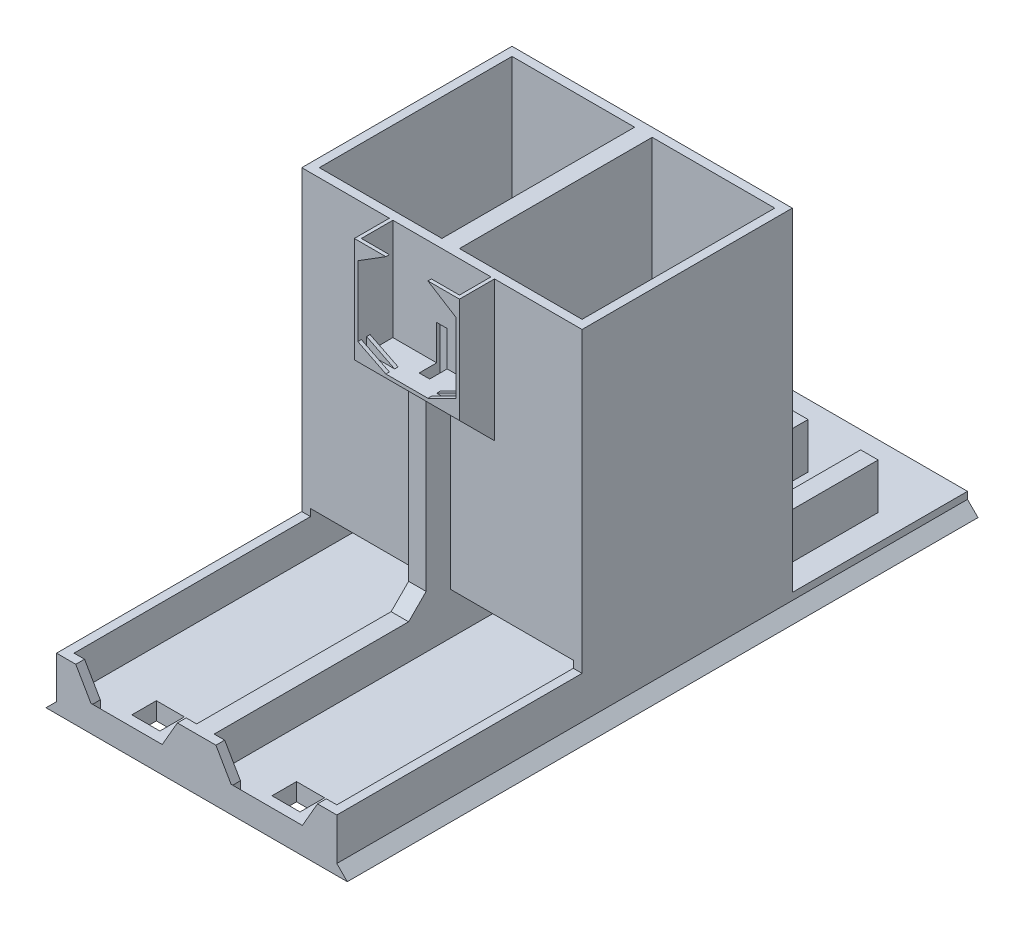
SolidWorks part; units mm, degrees
ref_plane "Front Plane" through (0, 0, 0) normal (0, 0, 1) x (1, 0, 0)
ref_plane "Top Plane" through (0, 0, 0) normal (0, 1, 0) x (1, 0, 0)
ref_plane "Right Plane" through (0, 0, 0) normal (1, 0, 0) x (0, 0, -1)
sketch "Sketch1" plane through (0, 0, 0) normal (0, 1, 0) x (1, 0, 0)
  line L1 (0, 0) -> (80, 0)
  line L2 (0, 0) -> (0, 60)
  line L3 (0, 60) -> (80, 60)
  line L4 (80, 0) -> (80, 60)
sketch "Sketch2" plane through (0, 0, 0) normal (0, 1, 0) x (1, 0, 0)
  line L1 (2.5, 57.5) -> (37.5, 57.5)
  line L2 (2.5, 57.5) -> (2.5, 2.5)
  line L3 (2.5, 2.5) -> (37.5, 2.5)
  line L4 (37.5, 57.5) -> (37.5, 2.5)
  line L5 (42.5, 57.5) -> (77.5, 57.5)
  line L6 (42.5, 57.5) -> (42.5, 2.5)
  line L7 (42.5, 2.5) -> (77.5, 2.5)
  line L8 (77.5, 57.5) -> (77.5, 2.5)
  dimension "D1" = 35
extrude "Boss-Extrude1" add sketch "Sketch1" along normal blind 100
extrude "Cut-Extrude1" cut sketch "Sketch2" along normal blind 95 from offset 5
sketch "Sketch3" plane through (0, 0, 0) normal (0, 0, 1) x (1, 0, 0)
  line L0 (80, 100) -> (80, 0) construction
  line L1 (0, 0) -> (80, 0)
  line L2 (0, 0) -> (0, 5)
  line L3 (0, 5) -> (80, 5)
  line L4 (80, 0) -> (80, 5)
extrude "Boss-Extrude2" add sketch "Sketch3" along normal blind 70
sketch "Sketch4" plane through (0, 5, 0) normal (0, 1, 0) x (1, 0, 0)
  line L0 (80, 0) -> (77.5, 0)
  line L5 (0, 0) -> (0, -70)
  line L18 (0, -70) -> (80, -70)
  line L19 (80, -70) -> (80, 0)
  line L20 (80, 0) -> (0, 0) construction
  line L21 (77.5, 0) -> (77.5, -67.5)
  line L22 (77.5, -67.5) -> (42.5, -67.5)
  line L23 (42.5, -67.5) -> (42.5, 0)
  line L24 (0, 0) -> (80, 0) construction
  line L25 (42.5, 0) -> (37.5, 0)
  line L26 (37.5, 0) -> (37.5, -67.5)
  line L27 (37.5, -67.5) -> (2.5, -67.5)
  line L28 (2.5, -67.5) -> (2.5, 0)
  line L29 (2.5, 0) -> (0, 0)
extrude "Boss-Extrude3" add sketch "Sketch4" along normal blind 10
sketch "Sketch5" plane through (0, 15, 0) normal (0, 1, 0) x (1, 0, 0)
  line L0 (37.5, -67.5) -> (2.5, -67.5) construction
  line L1 (10, -67.5) -> (30, -67.5)
  line L2 (10, -67.5) -> (10, -70)
  line L3 (10, -70) -> (30, -70)
  line L4 (30, -67.5) -> (30, -70)
  line L5 (0, -70) -> (80, -70) construction
  line L6 (77.5, -67.5) -> (42.5, -67.5) construction
  line L7 (70, -67.5) -> (50, -67.5)
  line L8 (70, -67.5) -> (70, -70)
  line L9 (70, -70) -> (50, -70)
  line L10 (50, -67.5) -> (50, -70)
  line L12 (37.5, 0) -> (37.5, -67.5) construction
  line L13 (42.5, -67.5) -> (42.5, 0) construction
  line L14 (77.5, 0) -> (77.5, -67.5) construction
  line L15 (2.5, -67.5) -> (2.5, 0) construction
  dimension "D1" = 7.5
  dimension "D2" = 7.5
  dimension "D3" = 7.5
  dimension "D4" = 7.5
extrude "Cut-Extrude2" cut sketch "Sketch5" against normal blind 7.5
sketch "Sketch6" plane through (0, 0, 0) normal (0, 0, 1) x (1, 0, 0)
  line L1 (2.5, 17) -> (37.5, 17)
  line L2 (2.5, 17) -> (2.5, 5)
  line L3 (2.5, 5) -> (37.5, 5)
  line L4 (37.5, 17) -> (37.5, 5)
  line L5 (42.5, 5) -> (77.5, 5)
  line L6 (42.5, 5) -> (42.5, 17)
  line L7 (42.5, 17) -> (77.5, 17)
  line L8 (77.5, 5) -> (77.5, 17)
extrude "Cut-Extrude4" cut sketch "Sketch6" against normal blind 57.5
sketch "Sketch7" plane through (0, 0, -60) normal (0, 0, -1) x (-1, 0, 0)
  circle A0 centre (-20, 11.5) radius 4
  circle A1 centre (-60, 11.5) radius 4
extrude "Cut-Extrude6" cut sketch "Sketch7" against normal up to next
sketch "Sketch9" plane through (0, 0, 0) normal (0, 1, 0) x (1, 0, 0)
  line L1 (0, 60) -> (80, 60)
  line L2 (0, 60) -> (0, 110)
  line L3 (0, 110) -> (80, 110)
  line L4 (80, 60) -> (80, 110)
extrude "Boss-Extrude4" add sketch "Sketch9" along normal blind 5
sketch "Sketch13" plane through (0, 5, 0) normal (0, 1, 0) x (1, 0, 0)
  line L1 (16, -64.5) -> (24, -64.5)
  line L2 (16, -64.5) -> (16, -57.5)
  line L3 (16, -57.5) -> (24, -57.5)
  line L4 (24, -64.5) -> (24, -57.5)
  line L5 (30, -67.5) -> (10, -67.5) construction
  line L10 (2.5, 57.5) -> (2.5, -67.5) construction
  line L11 (37.5, -67.5) -> (37.5, 57.5) construction
  line L12 (40, -70) -> (40, -52.9537) construction
  line L13 (30, -70) -> (50, -70) construction
  line L15 (56, -64.5) -> (56, -57.5)
  line L16 (64, -57.5) -> (56, -57.5)
  line L17 (64, -64.5) -> (64, -57.5)
  line L18 (64, -64.5) -> (56, -64.5)
  point P12 (16, -61)
  dimension "D1" = 13.5
  dimension "D2" = 13.5
  dimension "D3" = 7
  dimension "D4" = 3
extrude "Cut-Extrude8 (Button Holes)" cut sketch "Sketch13" against normal through all
sketch "Sketch14" plane through (0, 0, 0) normal (0, 0, 1) x (1, 0, 0)
  line L0 (0, 100) -> (80, 100) construction
  line L1 (25, 100) -> (26, 100)
  line L2 (25, 100) -> (25, 70)
  line L3 (25, 70) -> (26, 70)
  line L4 (26, 100) -> (26, 71)
  line L6 (54, 100) -> (55, 100)
  line L7 (54, 100) -> (54, 71)
  line L8 (54, 70) -> (55, 70)
  line L9 (55, 100) -> (55, 70)
  line L10 (26, 70) -> (54, 70)
  line L12 (26, 71) -> (54, 71)
  dimension "D1" = 30
  dimension "D2" = 1
  dimension "D3" = 1
extrude "Boss-Extrude5 (OLED Mount)" add sketch "Sketch14" along normal blind 10
sketch "Sketch15" plane through (0, 0, 10) normal (0, 0, 1) x (1, 0, 0)
  line L6 (40, 70) -> (40, 81.9127) construction
  line L7 (25, 70) -> (55, 70) construction
  line L8 (26, 71) -> (26, 100) construction
  line L14 (26, 71) -> (34, 71)
  line L15 (54, 71) -> (26, 71) construction
  line L16 (34, 71) -> (26, 75)
  line L17 (26, 75) -> (26, 71)
  line L18 (54, 75) -> (54, 71)
  line L19 (46, 71) -> (54, 75)
  line L20 (54, 71) -> (46, 71)
  dimension "D1" = 8
  dimension "D2" = 4
  dimension "D3" = 14
sketch "Sketch17" plane through (0, 0, 10) normal (0, 0, 1) x (1, 0, 0)
  line L0 (40, 100) -> (40, 89.7245) construction
  line L9 (26, 100) -> (54, 100) construction
  line L10 (54, 95) -> (54, 100)
  line L11 (46, 100) -> (54, 95)
  line L12 (26, 100) -> (34, 100)
  line L13 (34, 100) -> (26, 95)
  line L14 (26, 71) -> (26, 100) construction
  line L15 (26, 95) -> (26, 100)
  line L16 (54, 100) -> (46, 100)
  dimension "D1" = 8
  dimension "D2" = 5
extrude "Boss-Extrude6 (OLED Mount)" add sketch "Sketch15" against normal blind 1
extrude "Boss-Extrude7 (OLED Mount)" add sketch "Sketch15<2>" against normal blind 1 from offset 2.5 offset against normal yes
sketch "Sketch15<2>" plane through (0, 0, 10) normal (0, 0, 1) x (1, 0, 0) same geometry as "Sketch15"
extrude "Boss-Extrude8 (OLED Mount)" add sketch "Sketch17" against normal blind 1
sketch "Sketch32" plane through (25, 0, 0) normal (-1, 0, 0) x (0, 0, 1)
  line L0 (0, 70) -> (10, 70)
  line L1 (10, 70) -> (0, 60)
  line L3 (0, 60) -> (0, 70)
  line L4 (0, 15) -> (0, 17) construction
extrude "Boss-Extrude13 OLED Mount Support)" add sketch "Sketch32" against normal blind 30
sketch "Sketch18" plane through (0, 71, 0) normal (0, 1, 0) x (1, 0, 0)
  line L0 (26, 0) -> (54, 0) construction
  line L5 (42.5, 57.5) -> (42.5, -67.5) construction
  line L8 (38.5, 1) -> (41.5, 1)
  line L9 (38.5, 1) -> (38.5, -5)
  line L10 (38.5, -5) -> (41.5, -5)
  line L11 (41.5, 1) -> (41.5, -5)
  line L12 (37.5, -67.5) -> (37.5, 57.5) construction
  dimension "D1" = 1
  dimension "D2" = 1
  dimension "D3" = 1
  dimension "D4" = 5
extrude "Cut-Extrude9 (OLED Cable)" cut sketch "Sketch18" against normal through all and the other way blind 10
sketch "Sketch31" plane through (0, 15, 0) normal (0, 1, 0) x (1, 0, 0)
  line L0 (37.5, 0) -> (38.5, 0)
  line L1 (38.5, 0) -> (38.5, -5)
  line L2 (38.5, -5) -> (41.5, -5)
  line L3 (41.5, -5) -> (41.5, 0)
  line L4 (41.5, 0) -> (42.5, 0)
  line L5 (42.5, 0) -> (42.5, -7)
  line L6 (42.5, -7) -> (37.5, -7)
  line L7 (37.5, 0) -> (37.5, -67.5) construction
  line L8 (37.5, -7) -> (37.5, 0)
  dimension "D1" = 2
extrude "Boss-Extrude12 (OLED Cable Guide)" add sketch "Sketch31" along normal up to next
sketch "Sketch20" plane through (0, 5, 0) normal (0, 1, 0) x (1, 0, 0)
  line L0 (0, 60) -> (80, 60) construction
  line L1 (62.5, 60) -> (57.5, 60)
  line L2 (62.5, 60) -> (62.5, 65)
  line L3 (62.5, 65) -> (57.5, 65)
  line L4 (57.5, 60) -> (57.5, 65)
  line L5 (80, 60) -> (80, 110) construction
  line L7 (40, 110) -> (40, 60) construction
  line L8 (80, 110) -> (0, 110) construction
  line L9 (17.5, 65) -> (22.5, 65)
  line L10 (22.5, 60) -> (22.5, 65)
  line L11 (17.5, 60) -> (22.5, 60)
  line L12 (17.5, 60) -> (17.5, 65)
  point P8 (60, 60)
  dimension "D1" = 5
  dimension "D2" = 17.5
  dimension "D3" = 5
  dimension "D4" = 40
extrude "Cut-Extrude10 (Solenoid Wire Hole)" cut sketch "Sketch20" against normal through all
sketch "Sketch21" plane through (0, 5, 0) normal (0, 1, 0) x (1, 0, 0)
  line L0 (62.5, 60) -> (80, 60) construction
  line L1 (67.5, 60) -> (72.5, 60)
  line L2 (67.5, 60) -> (67.5, 92)
  line L3 (67.5, 92) -> (72.5, 92)
  line L4 (72.5, 60) -> (72.5, 92)
  line L7 (80, 110) -> (0, 110) construction
  line L9 (40, 60) -> (40, 110) construction
  line L10 (22.5, 60) -> (57.5, 60) construction
  line L11 (0, 110) -> (0, 60) construction
  line L12 (60, 110) -> (60, 60) construction
  line L13 (80, 60) -> (80, 110) construction
  line L15 (47.5, 60) -> (47.5, 92)
  line L16 (52.5, 92) -> (47.5, 92)
  line L17 (52.5, 60) -> (52.5, 92)
  line L18 (52.5, 60) -> (47.5, 60)
  line L19 (27.5, 60) -> (32.5, 60)
  line L20 (27.5, 60) -> (27.5, 92)
  line L21 (32.5, 60) -> (32.5, 92)
  line L22 (27.5, 92) -> (32.5, 92)
  line L23 (7.5, 60) -> (7.5, 92)
  line L24 (12.5, 92) -> (7.5, 92)
  line L25 (12.5, 60) -> (12.5, 92)
  line L26 (12.5, 60) -> (7.5, 60)
  dimension "D1" = 5
  dimension "D2" = 40
  dimension "D3" = 20
  dimension "D4" = 7.5
  dimension "D5" = 32
extrude "Boss-Extrude9 (Solenoid Side Support)" add sketch "Sketch21" along normal blind 13
chamfer "Chamfer3 (Thumb)" distance 2.5 angle 45 2 edges at (20, 7.5, 67.5) (60, 7.5, 67.5)
chamfer "Chamfer5 (Thumb)" distance 4.5 angle 60 4 edges at (70, 15, 68.75) (50, 15, 68.75) (30, 15, 68.75) (10, 15, 68.75) first distance on face at (75.8333, 15, 45.8333) first distance on face at (40, 15, 53) first distance on face at (4.1667, 15, 45.8333)
sketch "Sketch37" plane through (0, 0, 70) normal (0, 0, 1) x (1, 0, 0)
  line L0 (80, 0) -> (83, 0)
  line L1 (83, 0) -> (80, 3)
  line L2 (80, 0) -> (80, 15) construction
  line L3 (80, 3) -> (80, 0)
  line L4 (0, 0) -> (-3, 0)
  line L5 (-3, 0) -> (0, 3)
  line L6 (0, 15) -> (0, 0) construction
  line L7 (0, 3) -> (0, 0)
  dimension "D1" = 3
  dimension "D2" = 3
  dimension "D3" = 3
  dimension "D4" = 3
extrude "Boss-Extrude5 (Guide)" add sketch "Sketch37" against normal through all
sketch "Sketch49" plane through (0, 15, 0) normal (0, 1, 0) x (1, 0, 0)
  line L0 (42.5, -67.5) -> (42.5, -7) construction
  line L1 (37.5, -7) -> (42.5, -7)
  line L2 (37.5, -7) -> (37.5, -12)
  line L3 (37.5, -12) -> (42.5, -12)
  line L4 (42.5, -7) -> (42.5, -12)
  dimension "D1" = 5
extrude "Boss-Extrude14" add sketch "Sketch49" along normal blind 5
chamfer "Chamfer8" distance 5 angle 45 1 edges at (40, 20, 12)
